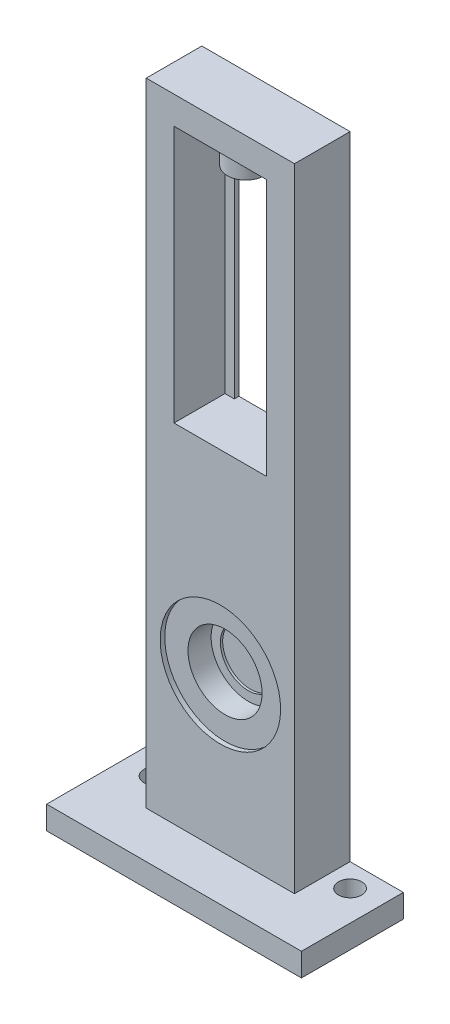
SolidWorks part; units mm, degrees
ref_plane "Front Plane" through (0, 0, 0) normal (0, 0, 1) x (1, 0, 0)
ref_plane "Top Plane" through (0, 0, 0) normal (0, 1, 0) x (1, 0, 0)
ref_plane "Right Plane" through (0, 0, 0) normal (1, 0, 0) x (0, 0, -1)
sketch "Sketch1" plane through (0, 0, 0) normal (0, 0, 1) x (1, 0, 0)
  line L0 (-16, 61.4754) -> (16, 61.4754)
  line L1 (10, 0) -> (16, 0)
  line L2 (10, 0) -> (10, 55.4754)
  line L4 (16, 0) -> (16, 61.4754)
  line L6 (-10, 55.4754) -> (-10, 0)
  line L7 (-10, 0) -> (-16, 0)
  line L8 (-16, 61.4754) -> (-16, 0)
  line L9 (-10, 55.4754) -> (10, 55.4754)
  line L12 (-10, 0) -> (10, 0) construction
  line L15 (-16, 55.4754) -> (-10, 55.4754) construction
  line L16 (10, 55.4754) -> (16, 55.4754) construction
  point P9 (0, 0)
  dimension "D1" = 6
  dimension "D2" = 6
  dimension "D3" = 20
extrude "MainFrame" add sketch "Sketch1" along normal blind 11
sketch "Sketch2" plane through (0, 0, 0) normal (0, 0, -1) x (-1, 0, 0)
  line L6 (8, 0) -> (8, 55.9754)
  line L7 (8, 55.9754) -> (-8, 55.9754)
  line L8 (-8, 55.9754) -> (-8, 0)
  line L9 (-16, 0) -> (-8, 0)
  line L10 (8, 0) -> (16, 0)
  line L11 (16, 61.4754) -> (16, 0) construction
  line L12 (-16, 61.4754) -> (16, 61.4754) construction
  line L13 (-16, 0) -> (-16, 61.4754) construction
  line L14 (16, 61.4754) -> (16, 0)
  line L15 (-16, 61.4754) -> (16, 61.4754)
  line L16 (-16, 0) -> (-16, 61.4754)
  line L18 (0, 55.9754) -> (0, 57.9754) construction
  line L19 (4.1066, 57.9754) -> (-4.1066, 57.9754) construction
  line L20 (8, 55.9754) -> (10, 55.9754) construction
  line L21 (10, 0) -> (10, 55.4754) construction
  line L22 (-8, 55.9754) -> (-10, 55.9754) construction
  line L23 (-10, 55.4754) -> (-10, 0) construction
  dimension "D1" = 2
extrude "GuideBackBoard" add sketch "Sketch2" along normal blind 1
sketch "Sketch3" plane through (0, 0, 0) normal (0, -1, 0) x (1, 0, 0)
  line L1 (16, 11) -> (-16, 11)
  line L2 (16, 11) -> (16, -1)
  line L3 (16, -1) -> (-16, -1)
  line L4 (-16, 11) -> (-16, -1)
extrude "LoweLength" add sketch "Sketch3" along normal blind 80
sketch "Sketch4" plane through (0, 0, 11) normal (0, 0, 1) x (1, 0, 0)
  line L0 (0, -42.0246) -> (0, 61.4754) construction
  line L1 (16, 61.4754) -> (-16, 61.4754) construction
  line L2 (0, 19.4754) -> (62.0349, 19.4754) construction
  circle A0 centre (0, -42.0246) radius 8
  dimension "D3" = 16
  dimension "D1" = 42
  dimension "D2" = 61.5
extrude "LowerCut Bearing Hole" cut sketch "Sketch4" against normal blind 6
sketch "Sketch6" plane through (0, 0, 5) normal (0, 0, 1) x (1, 0, 0)
  circle A1 centre (0, -42.0246) radius 6
  dimension "D1" = 12
extrude "Lower Bearing Hole1" cut sketch "Sketch6" against normal blind 0.5
sketch "Sketch7" plane through (0, 0, 11) normal (0, 0, 1) x (1, 0, 0)
  circle A0 centre (0, -42.0246) radius 13
  dimension "D1" = 26
extrude "Lower Bearing Hole 2" cut sketch "Sketch7" against normal blind 1
sketch "Sketch8" plane through (0, 0, -1) normal (0, 0, -1) x (-1, 0, 0)
  line L1 (-16, 61.4754) -> (-16, -80) construction
  line L5 (-16, 52.4554) -> (-16, -80)
  line L6 (-9.8987, 50.2254) -> (9.8987, 50.2254) construction
  arc A0 (-16, 52.4554) -> (-16, -80) centre (40.9093, -13.7723) ccw
  dimension "D1" = 2.23
extrude "BackBoardPlate" [suppressed] add sketch "Sketch8" against normal blind 1
sketch3d "3DSketch2" [suppressed]
  line L0 (43.6244, -21.2848, 0) -> (43.6244, -21.2848, 92.635) construction
  line L1 (28.0727, -5.0996, 0) -> (28.0727, -5.0996, 92.635) construction
  line L2 (16, 52.4554, -1) -> (16, 52.4554, 0)
  line L3 (16, -80, 0) -> (16, -80, -1)
  line L4 (16, 52.4554, -1) -> (16, 52.4554, 0)
  line L5 (16, -80, 0) -> (16, -80, -1)
  line L6 (28.0727, -37.47, 0) -> (28.0727, -37.47, 92.635) construction
  line L7 (28.0727, -5.0996, 92.635) -> (28.0727, -37.47, 92.635) construction
  line L8 (43.6244, -21.2848, 92.635) -> (28.0727, -21.2848, 92.635) construction
  line L9 (16, -80, 0) -> (16, 52.4554, 0) construction
  line L10 (16, 52.4554, 0) -> (16, 50.4554, 0)
  line L11 (16, -78, 0) -> (16, -80, 0)
  arc A0 (16, 52.4554, 0) -> (16, -80, 0) centre (-40.9093, -13.7723, 0) ccw construction
  arc A1 (16, 52.4554, 0) -> (16, -80, 0) centre (-40.9093, -13.7723, 0) ccw
  arc A2 (16, -80, -1) -> (16, 52.4554, -1) centre (-40.9093, -13.7723, -1) ccw
  arc A3 (16, 52.4554, 0) -> (16, -80, 0) centre (-40.9093, -13.7723, 0) ccw
  arc A4 (16, -80, -1) -> (16, 52.4554, -1) centre (-40.9093, -13.7723, -1) ccw
  arc A6 (16, -78, 0) -> (16, 50.4554, 0) centre (-42.9093, -13.7723, 0) cw
  point P7 (-40.9093, -13.7723, 86.3199)
  point P11 (-40.9093, -13.7723, -87.3199)
  point P12 (-40.9093, -13.7723, 86.3199)
  point P16 (28.0727, -5.0996, 40.0336)
  point P18 (28.0727, -37.47, 39.7995)
  point P19 (43.6244, -21.2848, 34.6355)
  point P22 (-40.9093, -13.7723, -87.3199)
  point P23 (-40.9093, -13.7723, -87.3199)
  point P24 (-42.9093, -13.7723, 87.1521)
  dimension "D3" = 2
  dimension "D2" = 2
  dimension "D1" = 0
extrude "FrontGuideHole" [suppressed] add sketch "3DSketch2" along direction (0, 0, 1) on the side of the normal blind 50 contours A1 L11 A6 L10
sketch "Sketch10" [suppressed] plane through (16, 0, 0) normal (1, 0, 0) x (0, 0, -1)
  line L0 (-1.7478, 52.4554) -> (-43.6495, 6.8734) construction
  line L1 (-11, 52.4554) -> (1, 52.4554) construction
  line L2 (-43.6495, 6.8734) -> (-26.9668, -11.2746) construction
  line L3 (-26.9668, -11.2746) -> (-43.6495, -29.4226) construction
  line L4 (-43.6495, -29.4226) -> (-1.7478, -80) construction
  line L5 (1, -80) -> (-11, -80) construction
  line L6 (-1.7478, -80) -> (-1.7478, 52.4554) construction
  line L7 (-43.6495, 6.8734) -> (-43.6495, -29.4226) construction
  line L8 (-1.7478, 52.4554) -> (-66.5911, 52.4554)
  line L9 (-66.5911, 52.4554) -> (-66.5911, -80)
  line L10 (-66.5911, -80) -> (-1.7478, -80)
  arc A0 (-43.6495, 6.8734) -> (-43.6495, -29.4226) centre (-54.1773, -11.2746) cw
  arc A1 (-43.6495, 6.8734) -> (-1.7478, 52.4554) centre (120.4526, -101.9287) cw
  arc A2 (-43.6495, -29.4226) -> (-1.7478, -80) centre (128.0845, 70.2075) ccw
  point P4 (-43.6495, -11.2746)
extrude "Front Guide Cut" [suppressed] cut sketch "Sketch10" along normal through all
ref_plane "Plane1" through (0, 0, 0) normal (1, 0, 0) x (0, 0, -1)
mirror "Mirror1" [suppressed] about plane through (0, 0, 0) normal (1, 0, 0)
sketch "Sketch11" plane through (0, 0, 11) normal (0, 0, 1) x (1, 0, 0)
  line L0 (0, -6.6) -> (0, 6.6) construction
  line L1 (-27.5, -80) -> (27.5, -80)
  line L2 (-27.5, -80) -> (-27.5, -75)
  line L3 (-27.5, -75) -> (27.5, -75)
  line L4 (27.5, -80) -> (27.5, -75)
  line L5 (16, -80) -> (-16, -80) construction
  point P4 (0, -75)
  dimension "D1" = 55
  dimension "D2" = 5
extrude "Boss-Extrude1" add sketch "Sketch11" along normal blind 10 and the other way up to surface (12 mm away) other way up to face at (0, 27.9877, -1)
sketch "Sketch12" plane through (0, -75, 0) normal (0, 1, 0) x (1, 0, 0)
  line L0 (0, 1) -> (0, -4) construction
  line L1 (-16, 1) -> (16, 1) construction
  line L2 (0, 0) -> (0, -11) construction
  line L3 (-21, -4) -> (21, -4) construction
  circle A0 centre (21, -4) radius 2.5
  circle A1 centre (-21, -4) radius 2.5
  point P11 (0, -4)
  dimension "D1" = 5
  dimension "D2" = 5
  dimension "D3" = 42
extrude "Cut-Extrude5" cut sketch "Sketch12" against normal through all
sketch "Sketch13" plane through (0, 55.4754, 0) normal (0, -1, 0) x (1, 0, 0)
  circle A0 centre (0, 5.5) radius 4
  circle A1 centre (0, 5.5) radius 1.5 construction
  dimension "D1" = 8
extrude "Boss-Extrude2" add sketch "Sketch13" along normal blind 5
